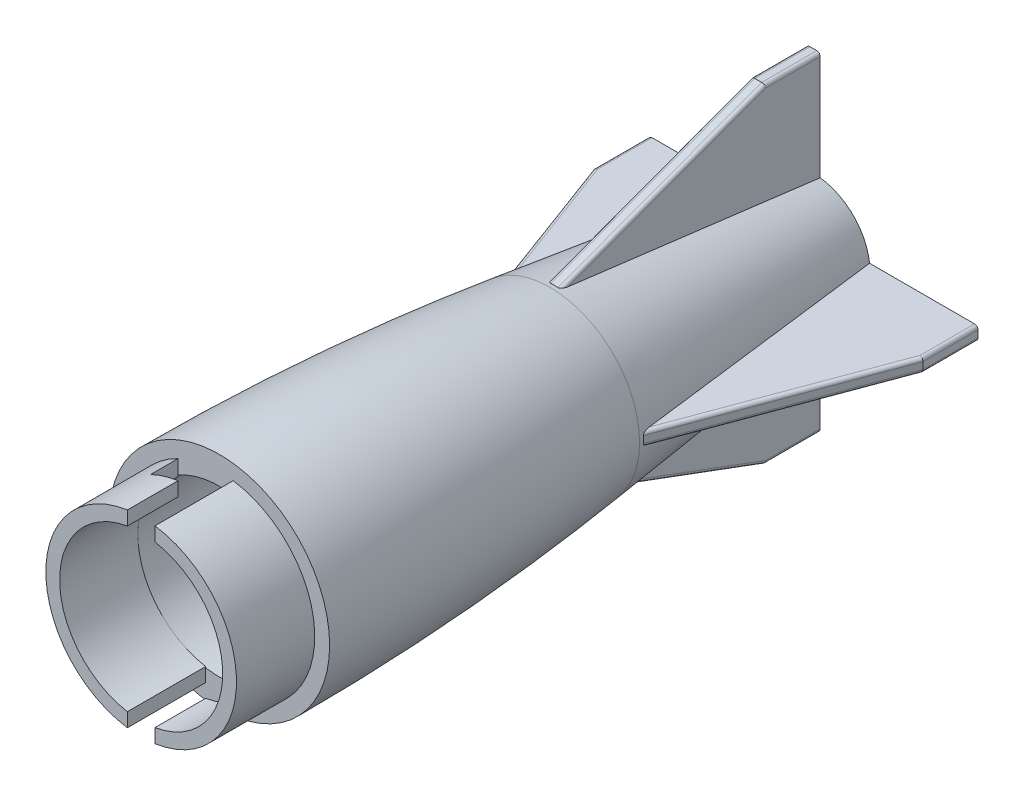
SolidWorks part; units mm, degrees
ref_plane "Front Plane" through (0, 0, 0) normal (0, 0, 1) x (1, 0, 0)
ref_plane "Top Plane" through (0, 0, 0) normal (0, 1, 0) x (1, 0, 0)
ref_plane "Right Plane" through (0, 0, 0) normal (1, 0, 0) x (0, 0, -1)
sketch "Sketch3" plane through (0, 0, 0) normal (1, 0, 0) x (0, 0, -1)
  line L0 (0, 0) -> (152.4, 0)
  line L1 (152.4, 0) -> (152.4, 3.175)
  line L2 (47.625, 0) -> (120.65, 0)
  line L3 (38.1, 12.7) -> (57.15, 12.7)
  line L5 (95.25, 10.3257) -> (152.4, 3.175)
  line L6 (0, 0) -> (0, 0.7937)
  line L7 (120.65, 0) -> (120.65, 3.9688)
  line L8 (120.65, 3.9688) -> (116.6813, 3.9687)
  line L9 (47.625, 9.525) -> (91.8932, 9.525)
  line L10 (120.65, 3.175) -> (122.2375, 3.175)
  line L11 (122.2375, 3.175) -> (125.5918, 6.5293)
  line L12 (57.15, 12.7) -> (57.15, 0)
  arc A1 (57.15, 12.7) -> (95.25, 10.3257) centre (57.15, -294.1784) cw
  arc A2 (0, 0.7937) -> (38.1, 12.7) centre (38.1, -54.2131) cw
  circle A3 centre (47.625, 0) radius 9.525
  arc A4 (91.8932, 9.525) -> (113.5348, 4.674) centre (91.8932, -41.1752) cw
  arc A5 (113.5348, 4.674) -> (116.6813, 3.9687) centre (116.6813, 11.3399) ccw
  dimension "D1" = 12.7
  dimension "D5" = 57.15
  dimension "D6" = 0.7937
  dimension "D8" = 73.025
  dimension "D9" = 19.05
  dimension "D2" = 38.1
  dimension "D3" = 3.175
  dimension "D4" = 19.05
  dimension "D7" = 152.4
  dimension "D10" = 3.9688
  dimension "D11" = 3.9688
  dimension "D12" = 31.75
  dimension "D13" = 1.5875
  dimension "D14" = 0.7937
  dimension "D15" = 135
revolve "Revolve2" add sketch "Sketch3" angle 360 about L0 region at (0, 11.1125, -57.841)
sketch "Sketch5" plane through (0, 0, 0) normal (1, 0, 0) x (0, 0, -1)
  line L1 (119.2418, 18.9753) -> (125.5918, 18.9753)
  line L2 (119.2418, 18.9753) -> (95.25, 10.0717)
  line L3 (125.5918, 18.9753) -> (125.5918, 6.2753)
  line L5 (125.5918, 6.5293) -> (125.5918, -6.5293) construction
  line L8 (125.5918, 6.2753) -> (95.25, 10.0717)
  line L9 (95.25, 10.0717) -> (95.25, -10.3257) construction
  line L10 (95.25, 10.3257) -> (95.25, -10.3257) construction
  point P2 (0, 0)
  point P5 (95.4448, 5.6458)
  point P8 (0, 0)
  point P9 (0, 0)
  point P11 (125.5918, 6.2753)
  point P12 (0, 0)
  point P15 (0, 0)
  point P16 (0, 0)
  point P19 (0, 0)
  dimension "D1" = 12.7
  dimension "D2" = 6.35
  dimension "D3" = 0.254
  dimension "D4" = 0.254
extrude "Boss-Extrude2" add sketch "Sketch5" along normal mid plane 1.5875 contours L8 L3 L1 L2 region at (0, 12.3157, -115.207)
fillet "Fillet2" radius 0.3969 4 edges at (0.7937, 18.9753, -122.4168) (-0.7937, 18.9753, -122.4168) (0.7937, 14.607, -107.4709) (-0.7937, 14.607, -107.4709)
pattern_circular "CirPattern5" count 4 over 360 about axis through (0, 0, -122.2375) along (0, 0, 1) of "Fillet2", "Boss-Extrude2"
sketch "Sketch6" plane through (0, 0, -57.15) normal (0, 0, 1) x (1, 0, 0)
  circle A0 centre (0, 0) radius 9.398
  circle A1 centre (0, 0) radius 10.9855
  dimension "D1" = 18.796
  dimension "D2" = 1.5875
extrude "Boss-Extrude3" add sketch "Sketch6" along normal blind 9.017
sketch "Sketch8" plane through (0, 0, 0) normal (0, 1, 0) x (1, 0, 0)
  line L0 (-10.9855, 48.133) -> (10.9855, 48.133) construction
  line L1 (1.5875, 39.116) -> (-1.5875, 39.116)
  line L2 (1.5875, 39.116) -> (1.5875, 57.15)
  line L3 (1.5875, 57.15) -> (-1.5875, 57.15)
  line L4 (-1.5875, 39.116) -> (-1.5875, 57.15)
  line L5 (1.5875, 39.116) -> (-1.5875, 57.15) construction
  line L6 (1.5875, 57.15) -> (-1.5875, 39.116) construction
  line L7 (-10.9855, 57.15) -> (10.9855, 57.15) construction
  line L9 (4.7625, 53.975) -> (-4.7625, 53.975)
  line L10 (4.7625, 53.975) -> (4.7625, 57.15)
  line L11 (4.7625, 57.15) -> (-4.7625, 57.15)
  line L12 (-4.7625, 53.975) -> (-4.7625, 57.15)
  line L13 (4.7625, 53.975) -> (-4.7625, 57.15) construction
  line L14 (4.7625, 57.15) -> (-4.7625, 53.975) construction
  point P0 (0, 48.133)
  point P9 (0, 55.5625)
  point P16 (0, 0)
  dimension "D1" = 3.175
  dimension "D2" = 3.175
  dimension "D3" = 9.525
extrude "Cut-Extrude1" cut sketch "Sketch8" against normal through all contours L2 L9 L4 L1 | L9 L2 L3 L4 | L10 L11 L2 L9 region at (0, 0, -46.5455) region at (0, 0, -55.5625) region at (3.175, 0, -55.5625)
extrude "Cut-Extrude2" cut sketch "Sketch8<3>" along normal up to surface (10.8702 mm away) contours L2 L9 L4 L1 | L9 L2 L3 L4 | L12 L9 L4 L11 region at (0, 0, -46.5455) region at (0, 0, -55.5625) region at (-3.175, 0, -55.5625) up to face at (1.0524, -3.3834, -53.086)
sketch "Sketch8<3>" plane through (0, 0, 0) normal (0, 1, 0) x (1, 0, 0) same geometry as "Sketch8"
